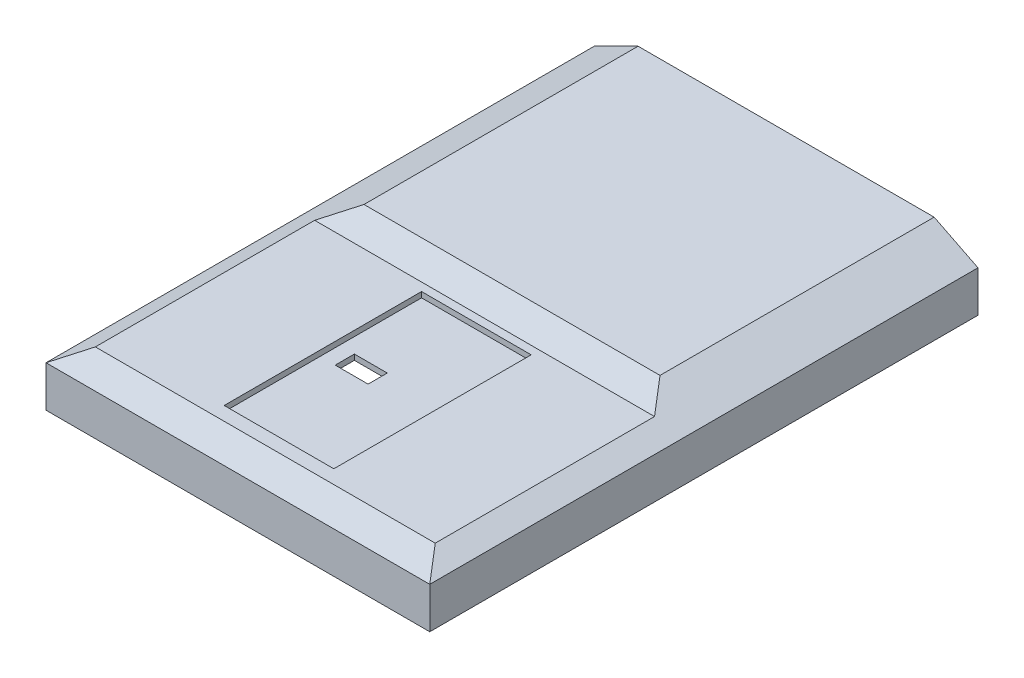
SolidWorks part; units mm, degrees
ref_plane "Ebene vorne" through (0, 0, 0) normal (0, 0, 1) x (1, 0, 0)
ref_plane "Ebene oben" through (0, 0, 0) normal (0, 1, 0) x (1, 0, 0)
ref_plane "Ebene rechts" through (0, 0, 0) normal (1, 0, 0) x (0, 0, -1)
sketch "Skizze1" plane through (0, 0, 0) normal (0, 0, 1) x (1, 0, 0)
  line L1 (-35, -7.5) -> (35, -7.5)
  line L2 (-35, -7.5) -> (-35, 7.5)
  line L3 (-35, 7.5) -> (35, 7.5)
  line L4 (35, -7.5) -> (35, 7.5)
  line L5 (-35, -7.5) -> (35, 7.5) construction
  line L6 (-35, 7.5) -> (35, -7.5) construction
  point P0 (0, 0)
  dimension "D1" = 70
  dimension "D2" = 15
extrude "Aufsatz-Linear austragen1" add sketch "Skizze1" along normal blind 100
sketch "Skizze2" plane through (0, 0, 100) normal (0, 0, 1) x (1, 0, 0)
  line L0 (-35, 7.5) -> (-35, 0)
  line L1 (-35, 7.5) -> (-35, -7.5) construction
  line L2 (-35, 0) -> (-20, 7.5)
  line L3 (35, 7.5) -> (-35, 7.5) construction
  line L4 (-20, 7.5) -> (-35, 7.5)
  dimension "D1" = 15
extrude "Schnitt-Linear austragen1" cut sketch "Skizze2" against normal up to surface (100 mm away) up to face at (0, 0, 0)
ref_plane "Ebene1" through (0, 0, 0) normal (-1, 0, 0) x (0, 0, 1)
mirror "Spiegeln1" about plane through (0, 0, 0) normal (-1, 0, 0) of "Schnitt-Linear austragen1"
sketch "Skizze4" plane through (-35, 0, 0) normal (-1, 0, 0) x (0, 0, 1)
  line L0 (100, 0) -> (95, 2)
  line L1 (95, 2) -> (55, 2)
  line L2 (55, 2) -> (50, 4)
  line L3 (50, 4) -> (0, 4)
  line L5 (0, 7.5) -> (100, 7.5) construction
  line L6 (0, 7.5) -> (100, 7.5)
  line L7 (100, 7.5) -> (100, 0)
  line L8 (0, 0) -> (0, 7.5) construction
  line L9 (0, 4) -> (0, 7.5)
  dimension "D1" = 2
  dimension "D2" = 2
  dimension "D3" = 40
  dimension "D4" = 50
extrude "Schnitt-Linear austragen3" cut sketch "Skizze4" against normal up to surface (70 mm away) up to face at (35, -3.75, 50)
shell "Wandung1" thickness 2 removed face at (0, -7.5, 50)
sketch "Skizze5" plane through (0, 2, 0) normal (0, 1, 0) x (1, 0, 0)
  line L0 (0, 4.125) -> (0, -4.125) construction
  line L1 (-10, -92.5) -> (10, -92.5)
  line L2 (-10, -92.5) -> (-10, -56.5)
  line L3 (-10, -56.5) -> (10, -56.5)
  line L4 (10, -92.5) -> (10, -56.5)
  line L5 (-10, -92.5) -> (10, -56.5) construction
  line L6 (-10, -56.5) -> (10, -92.5) construction
  line L7 (31, -55) -> (-31, -55) construction
  point P0 (0, -74.5)
  dimension "D1" = 36
  dimension "D2" = 20
  dimension "D3" = 1.5
extrude "Schnitt-Linear austragen4" cut sketch "Skizze5" against normal blind 1
sketch "Skizze6" plane through (0, 1, 0) normal (0, 1, 0) x (1, 0, 0)
  line L0 (-10, -56.5) -> (-10, -92.5) construction
  line L1 (-7.25, -71.5) -> (-1.25, -71.5)
  line L2 (-7.25, -71.5) -> (-7.25, -75)
  line L3 (-7.25, -75) -> (-1.25, -75)
  line L4 (-1.25, -71.5) -> (-1.25, -75)
  line L5 (10, -56.5) -> (-10, -56.5) construction
  dimension "D1" = 2.75
  dimension "D2" = 15
  dimension "D3" = 3.5
  dimension "D4" = 6
extrude "Schnitt-Linear austragen5" cut sketch "Skizze6" against normal up to surface (1 mm away) up to face at (0, 0, 74.6148)
